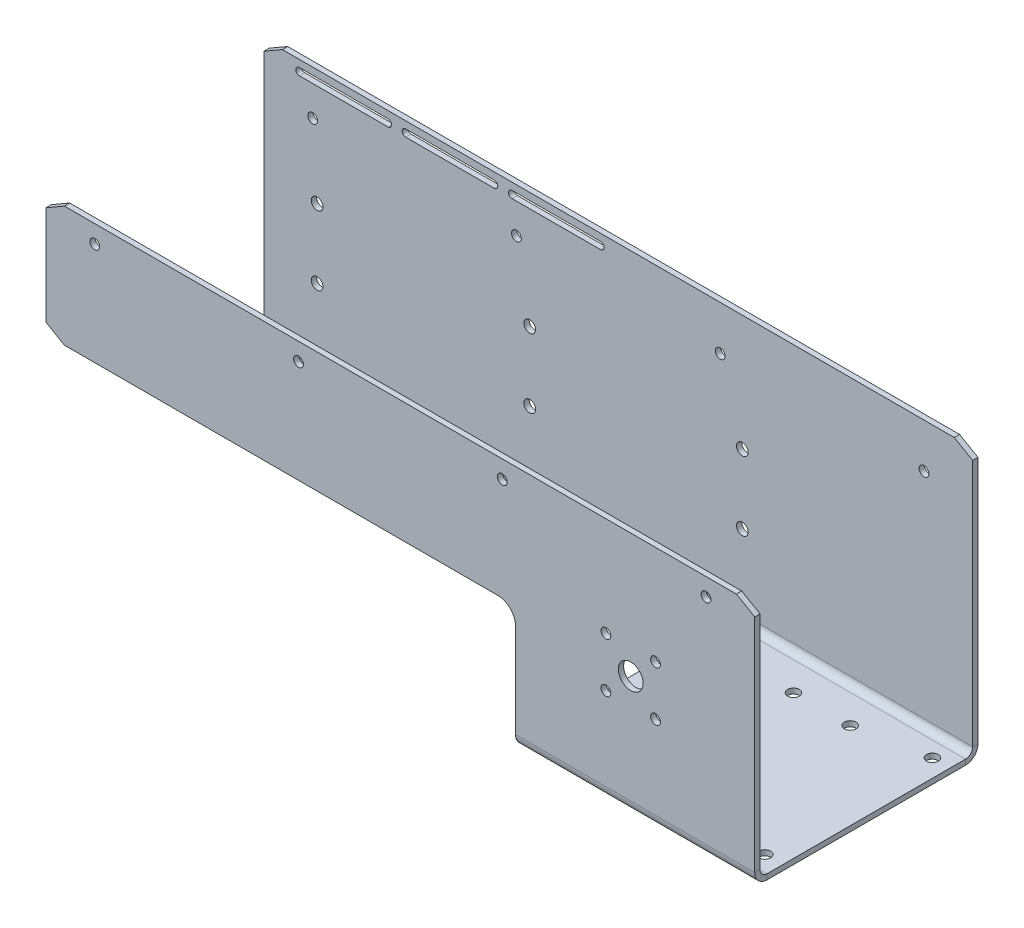
SolidWorks part; units mm, degrees
note: The reader was unsure of these and kept them because the rebuilt part matched: bend radius of "Zgięcie bazowe1", "Zgięcie bazowe2".
material "7075-O (SS)"
ref_plane "Płaszczyzna przednia" through (0, 0, 0) normal (0, 0, 1) x (1, 0, 0)
ref_plane "Płaszczyzna górna" through (0, 0, 0) normal (0, 1, 0) x (1, 0, 0)
ref_plane "Płaszczyzna prawa" through (0, 0, 0) normal (1, 0, 0) x (0, 0, -1)
sketch "Szkic1" plane through (0, 0, 0) normal (1, 0, 0) x (0, 0, -1)
  line L0 (-60, 0) -> (60, 0)
  line L1 (60, 0) -> (60, 150)
  line L2 (-60, 0) -> (-60, 135)
  dimension "D1" = 120
  dimension "D2" = 135
  dimension "D3" = 150
base flange "Odgięcie bazowe1" sketch "Szkic1" end condition mid plane depth 400 reverse direction no thickness 3 reverse thickness direction yes bend radius 4
bend "Zgięcie bazowe1" bend radius 4 bend angle 90 parameters "D5"=1
bend "Zgięcie bazowe2" bend radius 4 bend angle 90 parameters "D5"=2
sketch "Szkic25" plane through (0, 0, 63) normal (0, 0, 1) x (1, 0, 0)
  line L1 (-200, -3) -> (65, -3)
  line L2 (-200, -3) -> (-200, 67)
  line L3 (-200, 67) -> (65, 67)
  line L4 (65, -3) -> (65, 67)
  dimension "D1" = 265
  dimension "D2" = 70
extrude "Wytnij-wyciągnięcie2" cut sketch "Szkic25" against normal blind 94
chamfer "Sfazowanie1" distance 6 angle 60 6 edges at (-200, -1.5, -31) (-200, 67, 61.5) (200, 150, -61.5) (200, 135, 61.5) (-200, 135, 61.5) (-200, 150, -61.5)
fillet "Zaokrąglenie1" radius 10 2 edges at (65, -1.5, -31) (65, 67, 61.5)
hole_wizard "Otwór pod śrubę M51" positions "Szkic30" profile "Szkic31" hole size "M5" standard "Ansi Metric"
sketch "Szkic30" plane through (0, 0, 63) normal (0, 0, 1) x (1, 0, 0)
  line L0 (116, 79) -> (144, 51) construction
  line L2 (116, 51) -> (144, 79) construction
  line L4 (200, -3) -> (65, -3) construction
  line L5 (200, 4) -> (200, 129) construction
  point P0 (144, 79)
  point P3 (116, 79)
  point P6 (144, 51)
  point P9 (116, 51)
  point P27 (130, 65)
  dimension "D1" = 28
  dimension "D2" = 28
  dimension "D3" = 68
  dimension "D4" = 70
sketch "Szkic31" plane through (144, 79, 63) normal (1, 0, 0) x (0, -1, 0)
  line L0 (0, 0) -> (0, 3)
  line L1 (0, 3) -> (2.75, 3)
  line L2 (2.75, 3) -> (2.75, 0)
  line L5 (2.75, 0) -> (0, 0)
  line L11 (0, -6.35) -> (0, 107.95) construction
  dimension "Średnica otworu na wylot" = 5.5
  dimension "Głębokość otworu na wylot" = 3
hole_wizard "Otwór pod śrubę M61" positions "Szkic32" profile "Szkic33" hole size "M6" standard "Ansi Metric"
sketch "Szkic32" plane through (0, 0, -63) normal (0, 0, -1) x (-1, 0, 0)
  point P0 (-70, 84.5)
  point P3 (-70, 45.5)
  point P6 (50, 84.5)
  point P9 (50, 45.5)
  point P12 (170, 84.5)
  point P15 (170, 45.5)
sketch "Szkic33" plane through (70, 84.5, -63) normal (1, 0, 0) x (0, 1, 0)
  line L0 (0, 0) -> (0, 3)
  line L1 (0, 3) -> (3.3, 3)
  line L2 (3.3, 3) -> (3.3, 0)
  line L5 (3.3, 0) -> (0, 0)
  line L11 (0, -6.35) -> (0, 107.95) construction
  dimension "Średnica otworu na wylot" = 6.6
  dimension "Głębokość otworu na wylot" = 3
hole_wizard "Otwór pod śrubę M52" positions "Szkic35" profile "Szkic36" hole size "M5" standard "Ansi Metric" end condition through all
sketch "Szkic35" plane through (0, 0, -63) normal (0, 0, -1) x (-1, 0, 0)
  point P0 (-172.5, 125)
  point P3 (-57.5, 125)
  point P6 (57.5, 125)
  point P9 (172.5, 125)
sketch "Szkic36" plane through (172.5, 125, -63) normal (1, 0, 0) x (0, 1, 0)
  line L0 (0, 0) -> (0, 126)
  line L1 (0, 126) -> (2.75, 126)
  line L2 (2.75, 126) -> (2.75, 0)
  line L5 (2.75, 0) -> (0, 0)
  line L11 (0, -6.35) -> (0, 107.95) construction
  dimension "Średnica otworu na wylot" = 5.5
  dimension "Głębokość otworu na wylot" = 126
hole_wizard "Otwór pod śrubę M62" positions "Szkic42" profile "Szkic41" hole size "M6" standard "Ansi Metric"
sketch "Szkic42" plane through (0, -3, 0) normal (0, -1, 0) x (-1, 0, 0)
  line L0 (0, 0) -> (50000, 0) construction
  line L1 (-190, 47.25) -> (-80, 47.25) construction
  line L3 (-135, 49.5564) -> (-135, 50049.5564) construction
  line L4 (-200, 56) -> (-200, -56) construction
  point P0 (-190, 47.25)
  point P2 (-80, 47.25)
  point P4 (-151, 39.85)
  point P6 (-119, 39.85)
  point P19 (-135, 47.25)
  point P23 (-190, -47.25)
  point P24 (-151, -39.85)
  point P25 (-119, -39.85)
  point P26 (-80, -47.25)
  dimension "D1" = 110
  dimension "D2" = 32
  dimension "D3" = 94.5
  dimension "D4" = 79.7
  dimension "D5" = 10
sketch "Szkic41" plane through (190, -3, -47.25) normal (1, 0, 0) x (0, 0, -1)
  line L0 (0, 0) -> (0, 11.9828)
  line L1 (0, 11.9828) -> (3.3, 10)
  line L2 (3.3, 10) -> (3.3, 0)
  line L5 (3.3, 0) -> (0, 0)
  line L10 (0, 11.9828) -> (-3.3, 10) construction
  line L11 (0, -6.35) -> (0, 107.95) construction
  dimension "Średnica otworu" = 6.6
  dimension "Głębokość otworu" = 10
  dimension "Kąt wiertła" = 118
sketch "Szkic43" plane through (0, 0, -63) normal (0, 0, -1) x (-1, 0, 0)
  line L0 (130, 144) -> (180, 144) construction
  line L1 (130, 146) -> (180, 146)
  line L2 (130, 142) -> (180, 142)
  line L3 (-189.6077, 150) -> (189.6077, 150) construction
  line L4 (200, 144) -> (200, 4) construction
  line L5 (70, 144) -> (120, 144) construction
  line L6 (70, 146) -> (120, 146)
  line L7 (70, 142) -> (120, 142)
  line L8 (10, 144) -> (60, 144) construction
  line L9 (10, 146) -> (60, 146)
  line L10 (10, 142) -> (60, 142)
  arc A0 (130, 146) -> (130, 142) centre (130, 144) ccw
  arc A1 (180, 142) -> (180, 146) centre (180, 144) ccw
  arc A2 (70, 146) -> (70, 142) centre (70, 144) ccw
  arc A3 (120, 142) -> (120, 146) centre (120, 144) ccw
  arc A4 (10, 146) -> (10, 142) centre (10, 144) ccw
  arc A5 (60, 142) -> (60, 146) centre (60, 144) ccw
  point P2 (155, 144)
  point P15 (95, 144)
  point P22 (35, 144)
  dimension "D3" = 50
  dimension "D4" = 20
  dimension "D6" = 60
  dimension "D1" = 4
  dimension "D2" = 4
  dimension "D5" = 3
extrude "Wytnij-wyciągnięcie3" cut sketch "Szkic43" against normal up to next
sketch "Szkic48" plane through (0, 0, 63) normal (0, 0, 1) x (1, 0, 0)
  line L0 (116, 79) -> (144, 51) construction
  line L1 (144, 79) -> (116, 51) construction
  circle A0 centre (130, 65) radius 7
  dimension "D1" = 14
extrude "Wytnij-wyciągnięcie4" cut sketch "Szkic48" against normal blind 10
sketch "Linie zgięcia1" [suppressed] plane through (0, 0, 0) normal (0, 1, 0) x (1, 0, 0)
sketch "Ramka-graniczna1" [suppressed] plane through (0, 0, 0) normal (0, 1, 0) x (1, 0, 0)
sheet metal parameters "Arkusz blachy2" thickness 3 parameters "D1"=2.6
flat pattern "Rozłożony model2" [suppressed]
sketch "Linie zgięcia2" plane through (0, -3, 0) normal (0, -1, 0) x (-1, 0, 0)
  line L0 (-150, 58.6201) -> (150, 58.6201) construction
  line L1 (150, -58.6201) -> (-150, -58.6201) construction
  line L2 (-150, 58.6201) -> (150, 58.6201) construction
  line L3 (150, -58.6201) -> (-150, -58.6201) construction
sketch3d "Ramka-graniczna2" [suppressed]
  line L0 (300, -131.2403, 0) -> (300, 247.2403, 0) construction
  line L1 (0, -131.2403, 0) -> (0, 247.2403, 0) construction
  line L2 (300, -131.2403, 0) -> (0, -131.2403, 0) construction
  line L3 (300, 247.2403, 0) -> (0, 247.2403, 0) construction
bend of the flat pattern "Rozłożone-<Zgięcie bazowe1>1"
bend of the flat pattern "Rozłożone-<Zgięcie bazowe2>1"
sheet metal parameters "Arkusz blachy7" thickness 3 parameters "D1"=2.6
flat pattern "Rozłożony model2"
sketch "Linie zgięcia2" plane through (0, -3, 0) normal (0, -1, 0) x (-1, 0, 0)
  line L0 (-200, 60.6201) -> (200, 60.6201) construction
  line L1 (-65, -60.6201) -> (-200, -60.6201) construction
  line L2 (-200, 60.6201) -> (200, 60.6201) construction
  line L3 (-65, -60.6201) -> (-200, -60.6201) construction
sketch3d "Ramka-graniczna2" [suppressed]
  line L0 (0, 251.2403, 0) -> (400, 251.2403, 0) construction
  line L1 (0, -131.2403, 0) -> (400, -131.2403, 0) construction
  line L2 (0, 251.2403, 0) -> (0, -131.2403, 0) construction
  line L3 (400, 251.2403, 0) -> (400, -131.2403, 0) construction
bend of the flat pattern "Rozłożone-<Zgięcie bazowe1>1"
bend of the flat pattern "Rozłożone-<Zgięcie bazowe2>1"
sheet metal parameters "Arkusz blachy8" thickness 3 parameters "D1"=2.6
flat pattern "Rozłożony model2"
sketch "Linie zgięcia2" plane through (0, -3, 0) normal (0, -1, 0) x (-1, 0, 0)
  line L0 (-200, 60.6201) -> (200, 60.6201) construction
  line L1 (-65, -60.6201) -> (-200, -60.6201) construction
  line L2 (-200, 60.6201) -> (200, 60.6201) construction
  line L3 (-65, -60.6201) -> (-200, -60.6201) construction
sketch3d "Ramka-graniczna2" [suppressed]
  line L0 (0, 251.2403, 0) -> (400, 251.2403, 0) construction
  line L1 (0, -131.2403, 0) -> (400, -131.2403, 0) construction
  line L2 (0, 251.2403, 0) -> (0, -131.2403, 0) construction
  line L3 (400, 251.2403, 0) -> (400, -131.2403, 0) construction
bend of the flat pattern "Rozłożone-<Zgięcie bazowe1>1"
bend of the flat pattern "Rozłożone-<Zgięcie bazowe2>1"
sheet metal parameters "Arkusz blachy9" thickness 3 parameters "D1"=2.6
flat pattern "Rozłożony model2"
sketch "Linie zgięcia2" plane through (0, -3, 0) normal (0, -1, 0) x (-1, 0, 0)
  line L0 (-200, 60.6201) -> (200, 60.6201) construction
  line L1 (-65, -60.6201) -> (-200, -60.6201) construction
  line L2 (-200, 60.6201) -> (200, 60.6201) construction
  line L3 (-65, -60.6201) -> (-200, -60.6201) construction
sketch3d "Ramka-graniczna2" [suppressed]
  line L0 (0, 251.2403, 0) -> (400, 251.2403, 0) construction
  line L1 (0, -131.2403, 0) -> (400, -131.2403, 0) construction
  line L2 (0, 251.2403, 0) -> (0, -131.2403, 0) construction
  line L3 (400, 251.2403, 0) -> (400, -131.2403, 0) construction
bend of the flat pattern "Rozłożone-<Zgięcie bazowe1>1"
bend of the flat pattern "Rozłożone-<Zgięcie bazowe2>1"
sheet metal parameters "Arkusz blachy10" thickness 3 parameters "D1"=2.6
flat pattern "Rozłożony model2"
sketch "Linie zgięcia2" plane through (0, -3, 0) normal (0, -1, 0) x (-1, 0, 0)
  line L0 (-200, 60.6201) -> (200, 60.6201) construction
  line L1 (-65, -60.6201) -> (-200, -60.6201) construction
  line L2 (-200, 60.6201) -> (200, 60.6201) construction
  line L3 (-65, -60.6201) -> (-200, -60.6201) construction
sketch3d "Ramka-graniczna2" [suppressed]
  line L0 (0, 251.2403, 0) -> (400, 251.2403, 0) construction
  line L1 (0, -131.2403, 0) -> (400, -131.2403, 0) construction
  line L2 (0, 251.2403, 0) -> (0, -131.2403, 0) construction
  line L3 (400, 251.2403, 0) -> (400, -131.2403, 0) construction
bend of the flat pattern "Rozłożone-<Zgięcie bazowe1>1"
bend of the flat pattern "Rozłożone-<Zgięcie bazowe2>1"
sheet metal parameters "Arkusz blachy11" thickness 3 parameters "D1"=2.6
flat pattern "Rozłożony model2"
sketch "Linie zgięcia2" plane through (0, -3, 0) normal (0, -1, 0) x (-1, 0, 0)
  line L0 (-200, 60.6201) -> (200, 60.6201) construction
  line L1 (-65, -60.6201) -> (-200, -60.6201) construction
  line L2 (-200, 60.6201) -> (200, 60.6201) construction
  line L3 (-65, -60.6201) -> (-200, -60.6201) construction
sketch3d "Ramka-graniczna2" [suppressed]
  line L0 (400, -136.2403, 0) -> (400, 266.2403, 0) construction
  line L1 (0, -136.2403, 0) -> (0, 266.2403, 0) construction
  line L2 (400, -136.2403, 0) -> (0, -136.2403, 0) construction
  line L3 (400, 266.2403, 0) -> (0, 266.2403, 0) construction
bend of the flat pattern "Rozłożone-<Zgięcie bazowe1>1"
bend of the flat pattern "Rozłożone-<Zgięcie bazowe2>1"
sheet metal parameters "Arkusz blachy12" thickness 3 parameters "D1"=2.6
flat pattern "Rozłożony model2"
sketch "Linie zgięcia2" plane through (0, -3, 0) normal (0, -1, 0) x (-1, 0, 0)
  line L0 (-200, 60.6201) -> (200, 60.6201) construction
  line L1 (-65, -60.6201) -> (-200, -60.6201) construction
  line L2 (-200, 60.6201) -> (200, 60.6201) construction
  line L3 (-65, -60.6201) -> (-200, -60.6201) construction
sketch3d "Ramka-graniczna2" [suppressed]
  line L0 (400, -136.2403, 0) -> (400, 271.2403, 0) construction
  line L1 (0, -136.2403, 0) -> (0, 271.2403, 0) construction
  line L2 (400, -136.2403, 0) -> (0, -136.2403, 0) construction
  line L3 (400, 271.2403, 0) -> (0, 271.2403, 0) construction
bend of the flat pattern "Rozłożone-<Zgięcie bazowe1>1"
bend of the flat pattern "Rozłożone-<Zgięcie bazowe2>1"
sheet metal parameters "Arkusz blachy14" thickness 3 parameters "D1"=2.6
flat pattern "Rozłożony model2"
sketch "Linie zgięcia2" plane through (0, -3, 0) normal (0, -1, 0) x (-1, 0, 0)
  line L0 (-200, 60.4022) -> (200, 60.4022) construction
  line L1 (-65, -60.4022) -> (-200, -60.4022) construction
  line L2 (-200, 60.4022) -> (200, 60.4022) construction
  line L3 (-65, -60.4022) -> (-200, -60.4022) construction
sketch3d "Ramka-graniczna2" [suppressed]
  line L0 (400, -135.8043, 0) -> (400, 270.8043, 0) construction
  line L1 (0, -135.8043, 0) -> (0, 270.8043, 0) construction
  line L2 (400, -135.8043, 0) -> (0, -135.8043, 0) construction
  line L3 (400, 270.8043, 0) -> (0, 270.8043, 0) construction
bend of the flat pattern "Rozłożone-<Zgięcie bazowe1>1"
bend of the flat pattern "Rozłożone-<Zgięcie bazowe2>1"
